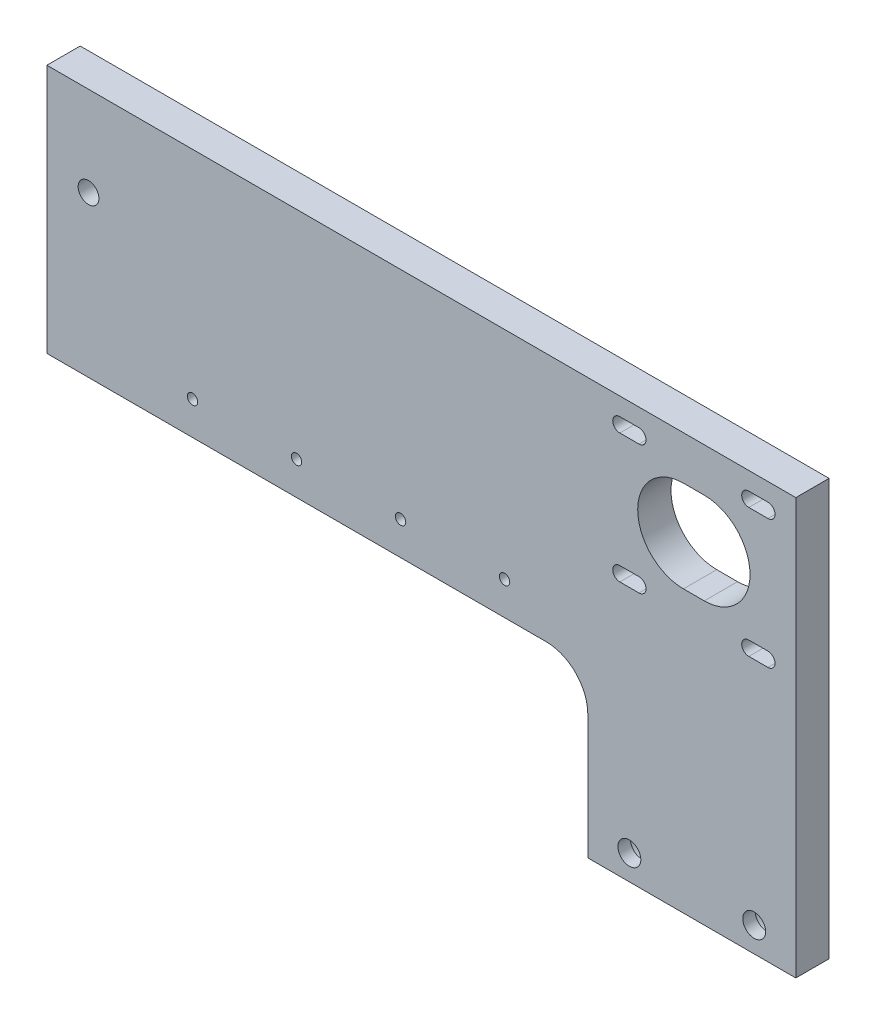
SolidWorks part; units mm, degrees
ref_plane "Front Plane" through (0, 0, 0) normal (0, 0, 1) x (1, 0, 0)
ref_plane "Top Plane" through (0, 0, 0) normal (0, 1, 0) x (1, 0, 0)
ref_plane "Right Plane" through (0, 0, 0) normal (1, 0, 0) x (0, 0, -1)
sketch "Sketch1" plane through (0, 0, 0) normal (0, 0, 1) x (1, 0, 0)
  line L6 (-180, 100) -> (0, 100)
  line L7 (0, 100) -> (0, 0)
  line L8 (0, 0) -> (-50, 0)
  line L9 (-50, 0) -> (-50, 30)
  line L10 (-60, 40) -> (-180, 40)
  line L11 (-180, 40) -> (-180, 100)
  arc A1 (-50, 30) -> (-60, 40) centre (-60, 30) ccw
  dimension "D9" = 10
  dimension "D6" = 180
  dimension "D7" = 100
  dimension "D8" = 60
  dimension "D10" = 50
extrude "BODY" add sketch "Sketch1" along normal blind 8
hole_wizard "M3 Clearance Slot1" positions "Sketch19" profile "Sketch20" size "M3" standard "ANSI Metric" slot yes end condition through all
sketch "Sketch19" plane through (0, 0, 8) normal (0, 0, 1) x (1, 0, 0)
  line L0 (-44, 94) -> (-36, 94) construction
  line L1 (0, 0) -> (0, 100) construction
  line L2 (0, 100) -> (-180, 100) construction
  point P0 (-40, 94)
  dimension "D1" = 8
  dimension "D2" = 40
  dimension "D3" = 6
sketch "Sketch20" plane through (-40, 94, 8) normal (1, 0, 0) x (0, -1, 0)
  line L0 (0, 0) -> (0, 8)
  line L1 (0, 8) -> (1.7, 8)
  line L2 (1.7, 8) -> (1.7, 0)
  line L5 (1.7, 0) -> (0, 0)
  line L11 (0, -6.35) -> (0, 107.95) construction
  dimension "Thru Hole Dia." = 3.4
  dimension "Thru Hole Depth" = 8
pattern_linear "LPattern3" count 2 spacing 31 along (1, 0, 0) count 2 spacing 31 along (0, -1, 0) of "M3 Clearance Slot1"
sketch "Sketch21" plane through (0, 0, 8) normal (0, 0, 1) x (1, 0, 0)
  line L0 (-40, 92.3) -> (-40, 64.7) construction
  line L1 (-42.3, 92.3) -> (-37.7, 92.3) construction
  line L2 (-42.3, 64.7) -> (-37.7, 64.7) construction
  line L3 (-40, 95.7) -> (-9, 95.7) construction
  line L4 (-42.3, 95.7) -> (-37.7, 95.7) construction
  line L5 (-11.3, 95.7) -> (-6.7, 95.7) construction
  line L6 (-27, 78.5) -> (-22, 78.5) construction
  line L7 (-27, 89.5) -> (-22, 89.5)
  line L8 (-27, 67.5) -> (-22, 67.5)
  arc A0 (-27, 89.5) -> (-27, 67.5) centre (-27, 78.5) ccw
  arc A1 (-22, 67.5) -> (-22, 89.5) centre (-22, 78.5) ccw
  point P14 (-24.5, 78.5)
  point P19 (0, 0)
  point P20 (-24.5, 95.7)
  point P21 (0, 0)
  point P22 (-40, 78.5)
  dimension "D1" = 11
  dimension "D2" = 5
extrude "Cut-Extrude1" cut sketch "Sketch21" against normal through all
hole_wizard "M3x0.5 Tapped Hole1" positions "Sketch11" profile "Sketch12" tap size "M3x0.5" standard "ANSI Metric" end condition through all
sketch "Sketch11" plane through (0, 0, 8) normal (0, 0, 1) x (1, 0, 0)
  line L0 (-180, 40) -> (-60, 40) construction
  line L1 (0, 0) -> (0, 100) construction
  point P0 (-70, 48)
  dimension "D1" = 8
  dimension "D2" = 70
sketch "Sketch12" plane through (-70, 48, 8) normal (1, 0, 0) x (0, -1, 0)
  line L0 (0, 0) -> (0, 8)
  line L1 (0, 8) -> (1.25, 8)
  line L2 (1.25, 8) -> (1.25, 0)
  line L5 (1.25, 0) -> (0, 0)
  line L11 (0, -6.35) -> (0, 107.95) construction
  dimension "Thru Tap Drill Dia." = 2.5
  dimension "Thru Tap Drill Depth" = 8
cosmetic thread "Hole Thread1" parameters "D2"=3
pattern_linear "LPattern2" count 4 spacing 25 along (-1, 0, 0) of "M3x0.5 Tapped Hole1"
cosmetic thread "Hole Thread2" parameters "D2"=3
cosmetic thread "Hole Thread3" parameters "D2"=3
cosmetic thread "Hole Thread4" parameters "D2"=3
hole_wizard "CBORE for M5 SHCS1" positions "Sketch10" profile "Sketch9" counterbore size "M5" standard "ANSI Metric" end condition through all
sketch "Sketch10" plane through (0, 0, 0) normal (0, 0, -1) x (-1, 0, 0)
  line L0 (0, 0) -> (0, 100) construction
  line L1 (50, 0) -> (0, 0) construction
  point P0 (10, 6)
  point P2 (40, 6)
  dimension "D1" = 10
  dimension "D2" = 6
  dimension "D3" = 30
sketch "Sketch9" plane through (-10, 6, 0) normal (1, 0, 0) x (0, 1, 0)
  line L0 (0, 0) -> (0, 8)
  line L1 (0, 8) -> (2.75, 8)
  line L3 (2.75, 8) -> (2.75, 5)
  line L4 (2.75, 5) -> (5, 5)
  line L5 (5, 5) -> (5, 0)
  line L7 (5, 0) -> (0, 0)
  line L11 (0, -6.35) -> (0, 107.95) construction
  dimension "Thru Hole Dia." = 5.5
  dimension "Thru Hole Depth" = 8
  dimension "C'Bore Dia." = 10
  dimension "C'Bore Depth" = 5
hole_wizard "M3x0.5 Tapped Hole2" positions "Sketch13" profile "Sketch14" tap size "M3x0.5" standard "ANSI Metric"
sketch "Sketch13" plane through (-180, 0, 0) normal (-1, 0, 0) x (0, 0, 1)
  line L0 (0, 100) -> (8, 100) construction
  line L1 (0, 100) -> (0, 40) construction
  point P0 (4, 82)
  point P2 (4, 76)
  dimension "D1" = 6
  dimension "D2" = 18
  dimension "D3" = 4
sketch "Sketch14" plane through (-180, 82, 4) normal (0, 1, 0) x (0, 0, 1)
  line L0 (0, 0) -> (0, 7.5)
  line L1 (0, 7.5) -> (1.25, 6.7489)
  line L2 (1.25, 6.7489) -> (1.25, 0)
  line L5 (1.25, 0) -> (0, 0)
  line L10 (0, 7.5) -> (-1.25, 6.7489) construction
  line L11 (0, -6.35) -> (0, 107.95) construction
  dimension "Tap Drill Dia." = 2.5
  dimension "Tap Drill Depth" = 7.5
  dimension "Drill Angle" = 118
cosmetic thread "Hole Thread5" parameters "D1"=6, "D2"=3
cosmetic thread "Hole Thread6" parameters "D1"=6, "D2"=3
sketch "Sketch22" plane through (0, 0, 8) normal (0, 0, 1) x (1, 0, 0)
  line L0 (-180, 100) -> (-180, 40) construction
  circle A0 centre (-170, 78.5) radius 2.5
  arc A1 (-27, 89.5) -> (-27, 67.5) centre (-27, 78.5) ccw construction
  point P2 (0, 0)
  point P6 (-38, 78.5)
  dimension "D1" = 5
  dimension "D2" = 10
extrude "Cut-Extrude2" cut sketch "Sketch22" against normal through all
